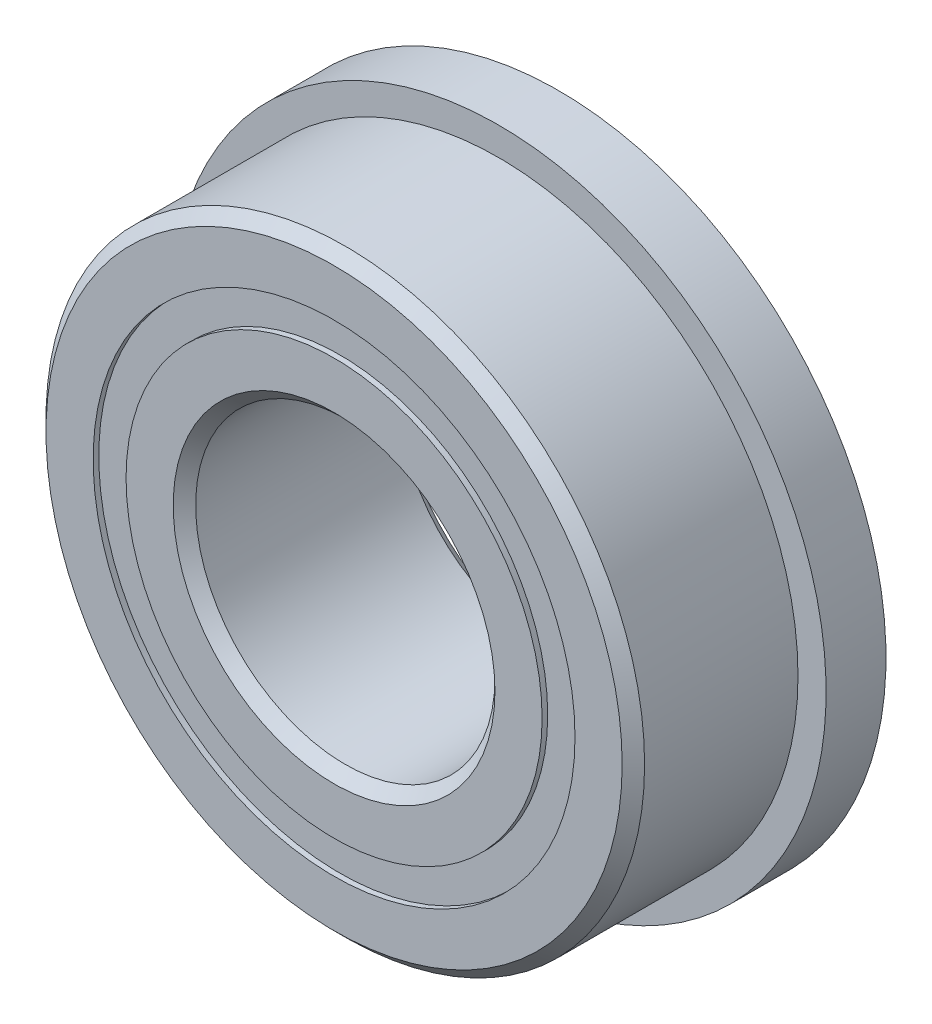
SolidWorks part; units mm, degrees
ref_plane "Front Plane" through (0, 0, 0) normal (0, 0, 1) x (1, 0, 0)
ref_plane "Top Plane" through (0, 0, 0) normal (0, 1, 0) x (1, 0, 0)
ref_plane "Right Plane" through (0, 0, 0) normal (1, 0, 0) x (0, 0, -1)
sketch "Sketch1" plane through (0, 0, 0) normal (1, 0, 0) x (0, 0, -1)
  line L0 (-2.3813, 0) -> (2.3813, 0) construction
  line L1 (0, 6.35) -> (0, -6.35) construction
  line L2 (2.1431, 6.35) -> (-2.1431, 6.35)
  line L3 (-2.1431, 6.35) -> (-2.3813, 6.1119)
  line L4 (-2.3813, 6.1119) -> (-2.3813, 5.1114)
  line L5 (-2.3813, 5.1114) -> (-1.0583, 5.1114)
  line L6 (2.3813, 5.1114) -> (1.0583, 5.1114)
  line L7 (2.3813, 6.1119) -> (2.3813, 5.1114)
  line L8 (2.1431, 6.35) -> (2.3813, 6.1119)
  line L9 (0, 6.35) -> (0, 4.7625) construction
  line L10 (0, 4.7625) -> (0, 3.175) construction
  arc A0 (-1.0583, 5.1114) -> (1.0583, 5.1114) centre (0, 4.7625) cw
  point P14 (0, 3.175)
  dimension "Width" = 4.7625
  dimension "OD" = 12.7
  dimension "D1" = 45
  dimension "D2" = 0.2381
  dimension "Shaft Dia" = 6.35
  dimension "D3" = 2.1167
  dimension "D4" = 0.3489
revolve "Revolve1" add sketch "Sketch1" angle 360 about L0
sketch "Sketch3" plane through (0, 0, 0) normal (1, 0, 0) x (0, 0, -1)
  line L0 (-2.3813, 4.4136) -> (-1.0583, 4.4136)
  line L1 (0, 6.35) -> (0, -6.35) construction
  line L2 (-2.3813, 6.1119) -> (-2.3813, 5.1114) construction
  line L3 (-2.3813, 4.4136) -> (-2.3813, 3.4131)
  line L4 (-2.1431, 6.35) -> (-2.3813, 6.1119) construction
  line L5 (-2.3813, 3.4131) -> (-2.1431, 3.175)
  line L6 (-2.1431, 3.175) -> (2.1431, 3.175)
  line L7 (2.1431, 6.35) -> (2.1431, -6.35) construction
  line L8 (2.1431, 3.175) -> (2.3813, 3.4131)
  line L9 (2.3813, -6.1119) -> (2.3813, 6.1119) construction
  line L10 (2.3813, 3.4131) -> (2.3813, 4.4136)
  line L11 (2.3813, 4.4136) -> (1.0583, 4.4136)
  line L13 (2.1431, 6.35) -> (2.3813, 6.1119) construction
  arc A0 (1.0583, 5.1114) -> (-1.0583, 5.1114) centre (0, 4.7625) ccw construction
  arc A1 (1.0583, 4.4136) -> (-1.0583, 4.4136) centre (0, 4.7625) cw
revolve "Revolve3" add sketch "Sketch3" angle 360 about L0
sketch "Sketch4" plane through (0, 0, 0) normal (1, 0, 0) x (0, 0, -1)
  line L0 (-1.1144, 4.7625) -> (1.1144, 4.7625)
  arc A2 (-1.1144, 4.7625) -> (1.1144, 4.7625) centre (0, 4.7625) cw
  arc A3 (1.0583, 5.1114) -> (-1.0583, 5.1114) centre (0, 4.7625) ccw construction
revolve "Revolve4" add sketch "Sketch4" angle 360 about L0
ref_axis "Axis1" through (0, 0, -2.3813) along (0, 0, 1)
pattern_circular "CirPattern1" count 12 every 30 about axis through (0, 0, -2.3813) along (0, 0, 1) of bodies 104
sketch "Sketch5" plane through (0, 0, 0) normal (1, 0, 0) x (0, 0, -1)
  line L0 (-2.3813, 5.1114) -> (-1.0583, 5.1114) construction
  line L1 (-2.2622, 5.1114) -> (-1.1144, 5.1114)
  line L2 (-2.2622, 5.1114) -> (-2.2622, 4.4136)
  line L3 (-2.2622, 4.4136) -> (-1.1144, 4.4136)
  line L4 (-1.1144, 5.1114) -> (-1.1144, 4.4136)
  line L5 (-2.3813, 4.4136) -> (-1.0583, 4.4136) construction
  line L6 (2.3813, 5.1114) -> (1.0583, 5.1114) construction
  line L7 (2.2622, 5.1114) -> (1.1144, 5.1114)
  line L8 (2.2622, 5.1114) -> (2.2622, 4.4136)
  line L9 (2.2622, 4.4136) -> (1.1144, 4.4136)
  line L10 (1.1144, 5.1114) -> (1.1144, 4.4136)
  line L11 (2.3813, 4.4136) -> (1.0583, 4.4136) construction
  line L12 (-2.1431, 6.35) -> (-2.3813, 6.1119) construction
  point P18 (-2.2622, 6.2309)
revolve "Revolve5" add sketch "Sketch5" angle 360 about L0
sketch "Sketch6" plane through (0, 0, 0) normal (1, 0, 0) x (0, 0, -1)
  line L0 (2.3813, 0) -> (-2.3813, 0) construction
  line L1 (2.3813, 5.1114) -> (1.1113, 5.1114)
  line L2 (2.3813, 5.1114) -> (2.3813, 6.9469)
  line L3 (2.3813, 6.9469) -> (1.1113, 6.9469)
  line L4 (1.1113, 5.1114) -> (1.1113, 6.9469)
  dimension "Th" = 1.27
  dimension "Flange OD" = 13.8938
revolve "Revolve6" add sketch "Sketch6" angle 360 about L0
equation "\"D2@Sketch1\" = \"Width@Sketch1\"*.05"
equation "\"D3@Sketch1\" = \"Width@Sketch1\"/2.25"
equation "\"D4@Sketch1\" = (((\"OD@Sketch1\"-\"Width@Sketch1\")/2)/3.25)/3.5"
equation "\"D2@CirPattern1\" = 360/\"Balls@CirPattern1\""
